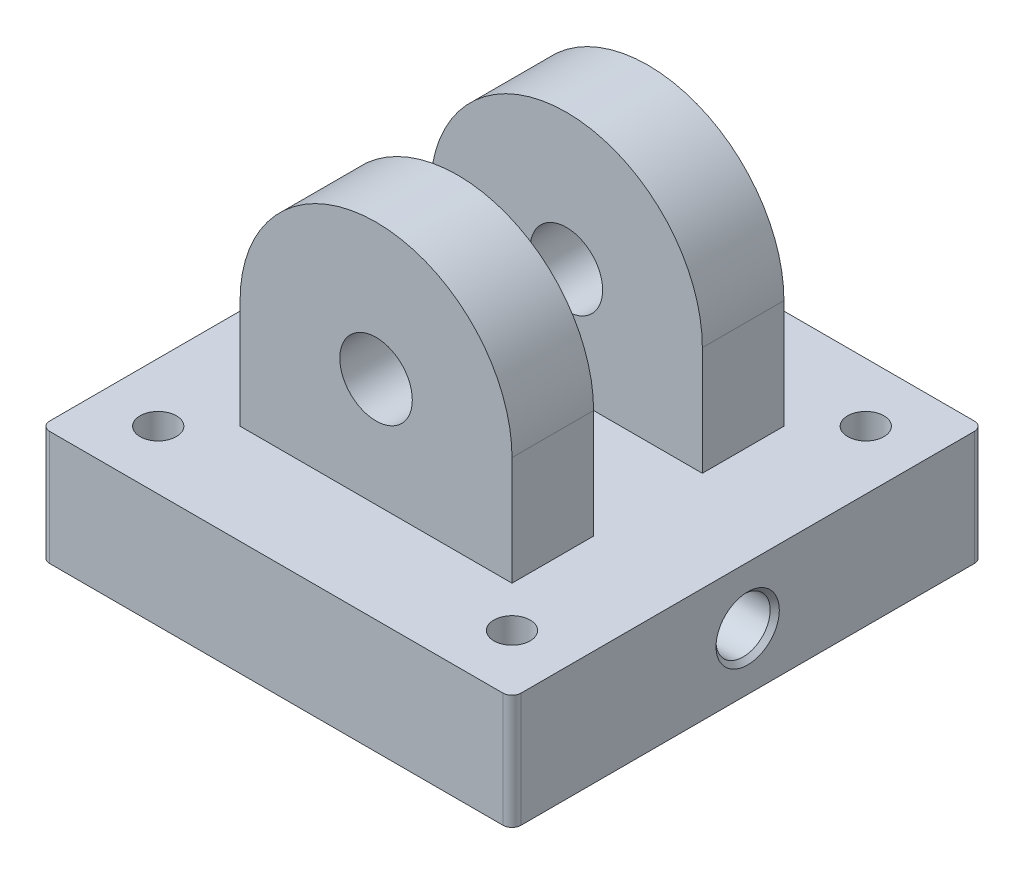
SolidWorks part; units mm, degrees
ref_plane "Front Plane" through (0, 0, 0) normal (0, 0, 1) x (1, 0, 0)
ref_plane "Top Plane" through (0, 0, 0) normal (0, 1, 0) x (1, 0, 0)
ref_plane "Right Plane" through (0, 0, 0) normal (1, 0, 0) x (0, 0, -1)
sketch "Sketch4" plane through (0, 0, 0) normal (0, 1, 0) x (1, 0, 0)
  line L1 (-82.55, 82.55) -> (82.55, 82.55)
  line L2 (-82.55, 82.55) -> (-82.55, -82.55)
  line L3 (-82.55, -82.55) -> (82.55, -82.55)
  line L4 (82.55, 82.55) -> (82.55, -82.55)
  line L5 (-82.55, 82.55) -> (82.55, -82.55) construction
  line L6 (-82.55, -82.55) -> (82.55, 82.55) construction
  point P0 (0, 0)
  dimension "D1" = 165.1
extrude "Boss-Extrude2" add sketch "Sketch4" along normal blind 38.1 and the other way blind 2
sketch "Sketch5" plane through (0, 38.1, 0) normal (0, 1, 0) x (1, 0, 0)
  line L1 (-47.625, 47.625) -> (47.625, 47.625)
  line L2 (-47.625, 47.625) -> (-47.625, -47.625)
  line L3 (-47.625, -47.625) -> (47.625, -47.625)
  line L4 (47.625, 47.625) -> (47.625, -47.625)
  line L5 (-47.625, 47.625) -> (47.625, -47.625) construction
  line L6 (-47.625, -47.625) -> (47.625, 47.625) construction
  point P0 (0, 0)
  dimension "D1" = 95.25
extrude "Boss-Extrude3" add sketch "Sketch5" along normal blind 38.1
sketch "Sketch6" plane through (0, 0, 47.625) normal (0, 0, 1) x (1, 0, 0)
  line L0 (-47.625, 76.2) -> (47.625, 76.2)
  arc A0 (47.625, 76.2) -> (-47.625, 76.2) centre (0, 76.2) ccw
  dimension "D1" = 47.625
extrude "Boss-Extrude4" add sketch "Sketch6" against normal up to vertex (95.25 mm away) up to point (47.625, 76.2, -47.625)
sketch "Sketch7" plane through (0, 0, 47.625) normal (0, 0, 1) x (1, 0, 0)
  circle A0 centre (0, 76.2) radius 12.7
  dimension "D1" = 25.4
extrude "Cut-Extrude1" cut sketch "Sketch7" against normal through all
sketch "Sketch8" plane through (47.625, 0, 0) normal (1, 0, 0) x (0, 0, -1)
  line L0 (-47.625, 38.1) -> (47.625, 38.1) construction
  line L1 (-19.05, 38.1) -> (19.05, 38.1)
  line L2 (-19.05, 38.1) -> (-19.05, 123.825)
  line L3 (-19.05, 123.825) -> (19.05, 123.825)
  line L4 (19.05, 38.1) -> (19.05, 123.825)
  line L5 (47.625, 123.825) -> (-47.625, 123.825) construction
  line L6 (-47.625, 123.825) -> (-47.625, 76.2) construction
  dimension "D1" = 38.1
  dimension "D2" = 28.575
extrude "Cut-Extrude2" cut sketch "Sketch8" against normal through all
fillet "Fillet1" radius 3.175 4 edges at (82.55, 18.05, 82.55) (-82.55, 18.05, 82.55) (-82.55, 18.05, -82.55) (82.55, 18.05, -82.55)
sketch "Sketch9" plane through (0, -2, 0) normal (0, -1, 0) x (1, 0, 0)
  circle A0 centre (0, 0) radius 26
  dimension "D1" = 52
extrude "Cut-Extrude3" cut sketch "Sketch9" against normal blind 36.83
sketch "Sketch10" plane through (0, -2, 0) normal (0, -1, 0) x (1, 0, 0)
  circle A0 centre (0, 0) radius 69.85
  circle A1 centre (0, 0) radius 76.2
  dimension "D1" = 152.4
  dimension "D2" = 139.7
extrude "Cut-Extrude4" cut sketch "Sketch10" against normal blind 8
sketch "Sketch11" plane through (82.55, 0, 0) normal (1, 0, 0) x (0, 0, -1)
  line L0 (-79.375, 18.05) -> (79.375, 18.05) construction
  line L1 (-79.375, 38.1) -> (-79.375, -2) construction
  line L2 (79.375, -2) -> (79.375, 38.1) construction
hole_wizard "1/2-14 NPSM Tapped Hole1" positions "Sketch12" profile "Sketch13" tap size "1/2-14 NPSM" standard "ANSI Inch"
sketch "Sketch12" plane through (82.55, 0, 0) normal (1, 0, 0) x (0, 0, -1)
  line L0 (-79.375, 18.05) -> (79.375, 18.05) construction
  point P0 (0, 18.05)
sketch "Sketch13" plane through (82.55, 18.05, 0) normal (0, 1, 0) x (0, 0, -1)
  line L0 (0, 0) -> (0, 69.2003)
  line L1 (0, 69.2003) -> (9.4869, 63.5)
  line L2 (9.4869, 63.5) -> (9.4869, 1.6002)
  line L3 (9.4869, 1.6002) -> (11.0871, 0)
  line L5 (11.0871, 0) -> (0, 0)
  line L6 (-9.4869, 1.6002) -> (-11.0871, 0) construction
  line L10 (0, 69.2003) -> (-9.4869, 63.5) construction
  line L11 (0, -6.35) -> (0, 107.95) construction
  dimension "Tap Drill Dia." = 18.9738
  dimension "Tap Drill Depth" = 63.5
  dimension "Near C'Sink Dia." = 22.1742
  dimension "Near C'Sink Angle" = 90
  dimension "Drill Angle" = 118
cosmetic thread "Hole Thread1" parameters "D1"=41.91, "D2"=20.9042
sketch "Sketch16" plane through (0, -2, 0) normal (0, -1, 0) x (1, 0, 0)
  line L0 (82.55, 79.375) -> (82.55, -79.375) construction
  circle A0 centre (50.55, 0) radius 6.35
  dimension "D1" = 12.7
  dimension "D2" = 32
extrude "Cut-Extrude5" cut sketch "Sketch16" against normal blind 25
sketch "Sketch17" plane through (0, -2, 0) normal (0, -1, 0) x (1, 0, 0)
  line L1 (-61.9638, 61.9638) -> (61.9638, 61.9638) construction
  line L2 (-61.9638, 61.9638) -> (-61.9638, -61.9638) construction
  line L3 (-61.9638, -61.9638) -> (61.9638, -61.9638) construction
  line L4 (61.9638, 61.9638) -> (61.9638, -61.9638) construction
  line L5 (-61.9638, 61.9638) -> (61.9638, -61.9638) construction
  line L6 (-61.9638, -61.9638) -> (61.9638, 61.9638) construction
  circle A0 centre (0, 0) radius 87.63 construction
  circle A1 centre (-61.9638, 61.9638) radius 6.35
  circle A2 centre (61.9638, 61.9638) radius 6.35
  circle A3 centre (61.9638, -61.9638) radius 6.35
  circle A4 centre (-61.9638, -61.9638) radius 6.35
  dimension "D1" = 175.26
  dimension "D2" = 12.7
extrude "Cut-Extrude6" cut sketch "Sketch17" against normal through all
